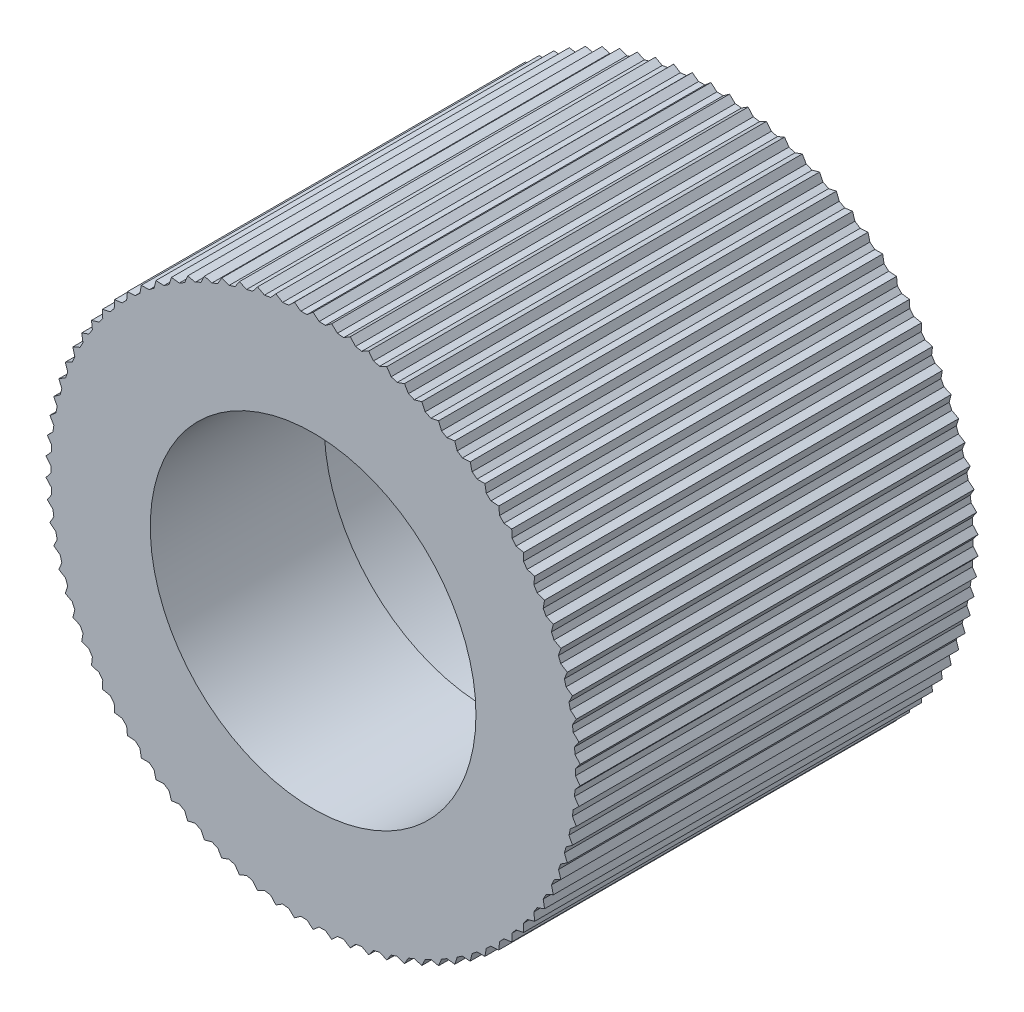
SolidWorks part; units mm, degrees
ref_plane "Alzado" through (0, 0, 0) normal (0, 0, 1) x (1, 0, 0)
ref_plane "Planta" through (0, 0, 0) normal (0, 1, 0) x (1, 0, 0)
ref_plane "Vista lateral" through (0, 0, 0) normal (1, 0, 0) x (0, 0, -1)
sketch "Croquis1" plane through (0, 0, 0) normal (0, 0, 1) x (1, 0, 0)
  circle A0 centre (0, 0) radius 3.275
  circle A1 centre (0, 0) radius 5.275
  dimension "D1" = 6.55
  dimension "D2" = 2
extrude "Saliente-Extruir1" add sketch "Croquis1" along normal mid plane 3.5
sketch "Croquis2" plane through (0, 0, -1.75) normal (0, 0, -1) x (-1, 0, 0)
  circle A0 centre (0, 0) radius 5.275 construction
  circle A1 centre (0, 0) radius 5.275
  circle A2 centre (0, 0) radius 3.975
  dimension "D1" = 1.3
extrude "Saliente-Extruir2" add sketch "Croquis2" along normal blind 4.5
sketch "Croquis6" plane through (0, 0, 0) normal (0, 0, 1) x (1, 0, 0)
  line L0 (0, -1.2864) -> (0, 7.503) construction
  line L1 (0, 5.275) -> (0, 5.375)
  line L2 (0, 5.375) -> (0.1208, 5.2736)
  line L3 (0, 5.375) -> (-0.1208, 5.2736)
  circle A0 centre (0, 0) radius 5.275 construction
  arc A1 (0.1208, 5.2736) -> (-0.1208, 5.2736) centre (0, 0) ccw
  dimension "D1" = 50
  dimension "D2" = 0.1
extrude "Saliente-Extruir3" add sketch "Croquis6" against normal through all and the other way through all contours A1 L2 L1 | A1 L1 L3 region at (-0.0402, 5.308, 0) region at (0.0402, 5.308, 0)
pattern_circular "MatrizC1" count 90 over 360 about axis through (0, 0, 1.75) along (0, 0, 1) of "Saliente-Extruir3"
